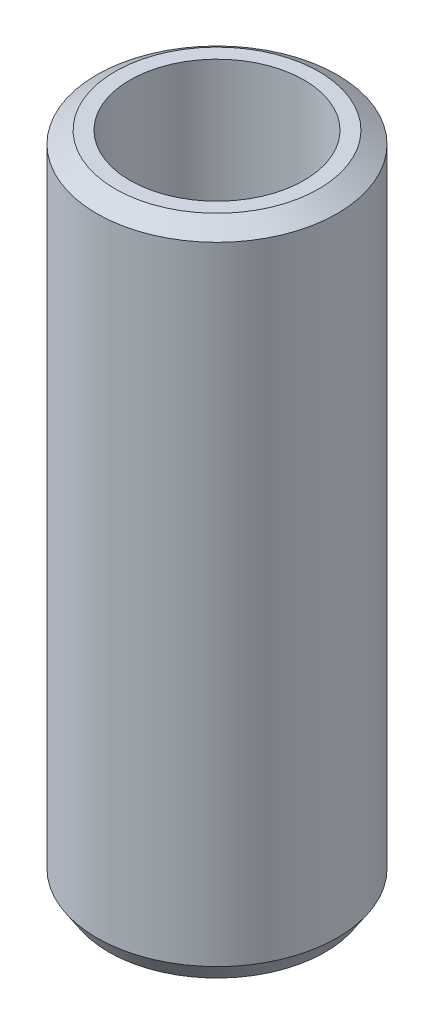
SolidWorks part; units mm, degrees
ref_plane "Front Plane" through (0, 0, 0) normal (0, 0, 1) x (1, 0, 0)
ref_plane "Top Plane" through (0, 0, 0) normal (0, 1, 0) x (1, 0, 0)
ref_plane "Right Plane" through (0, 0, 0) normal (1, 0, 0) x (0, 0, -1)
sketch "Sketch1" plane through (0, 0, 0) normal (0, 1, 0) x (1, 0, 0)
  circle A0 centre (0, 0) radius 25
  dimension "SHAFT_OD" = 50
extrude "Boss-Extrude1" add sketch "Sketch1" along normal blind 136.762
sketch "Sketch2" plane through (0, 0, 0) normal (0, 1, 0) x (1, 0, 0)
  circle A0 centre (0, 0) radius 18.0928
  dimension "BORE_D" = 36.1856
extrude "Cut-Extrude1" cut sketch "Sketch2" along normal through all
chamfer "Chamfer1" distance 2.5188 angle 56.713 2 edges at (0, 136.762, 25) (0, 0, 25) first distance on face at (0, 136.762, 25) first distance on face at (0, 0, 18.0928)
